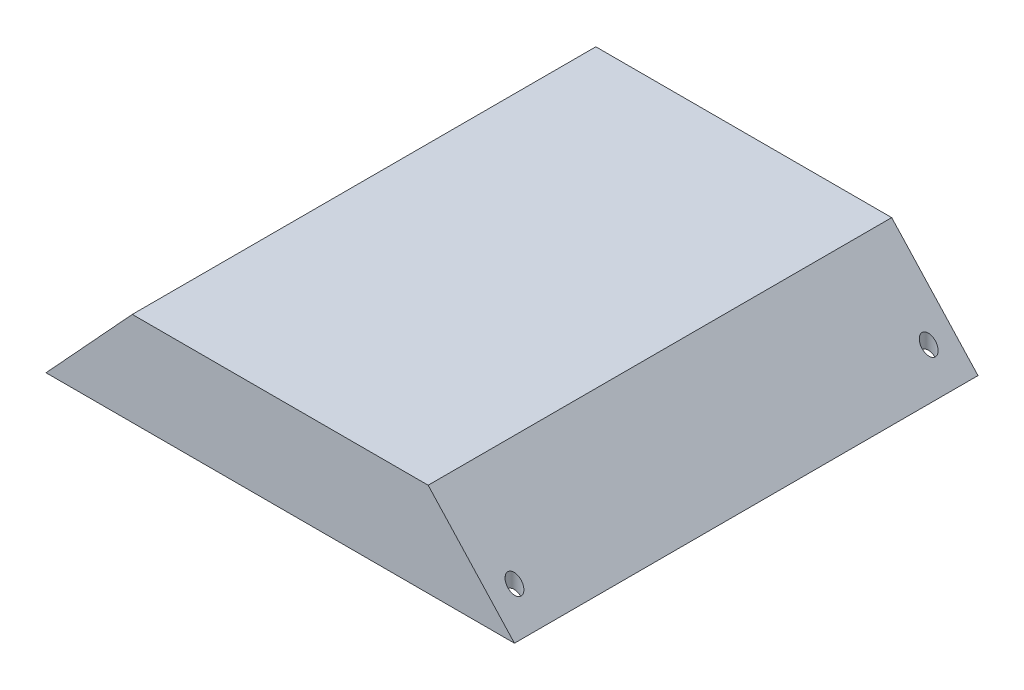
SolidWorks part; units mm, degrees
ref_plane "Alzado" through (0, 0, 0) normal (0, 0, 1) x (1, 0, 0)
ref_plane "Planta" through (0, 0, 0) normal (0, 1, 0) x (1, 0, 0)
ref_plane "Vista lateral" through (0, 0, 0) normal (1, 0, 0) x (0, 0, -1)
sketch "Croquis2" plane through (0, 0, 0) normal (0, 0, 1) x (1, 0, 0)
  line L0 (-47.5, 0) -> (-30, 0)
  line L1 (-30, 0) -> (-30, 19)
  line L2 (-30, 19) -> (-47.5, 0)
  line L3 (30, 19) -> (47.5, 0)
  line L4 (-30, 19) -> (30, 19)
  line L5 (-30, 19) -> (-30, 0)
  line L6 (-30, 0) -> (30, 0)
  line L7 (30, 19) -> (30, 0)
  line L8 (47.5, 0) -> (30, 0)
  dimension "D1" = 95
  dimension "D2" = 60
  dimension "D3" = 19
extrude "Saliente-Extruir1" add sketch "Croquis2" along normal blind 94 contours L7 L4 L1 L6 | L1 L2 L0 | L8 L3 L7 region at (-35.8333, 6.3333, 0) region at (0, 9.5, 0) region at (35.8333, 6.3333, 0)
sketch "Croquis3" plane through (0, 0, 0) normal (0, 0, -1) x (-1, 0, 0)
  line L0 (-44.7368, 0) -> (-30, 16)
  line L1 (47.5, 0) -> (-47.5, 0) construction
  line L2 (-30, 16) -> (30, 16)
  line L3 (30, 16) -> (44.7368, 0)
  line L4 (44.7368, 0) -> (-44.7368, 0)
  line L5 (-30, 19) -> (-47.5, 0) construction
  line L6 (30, 19) -> (-30, 19) construction
  line L7 (30, 19) -> (47.5, 0) construction
  line L11 (47.5, 0) -> (44.7368, 0)
  line M1 (-47.5, 0) -> (47.5, 0)
  dimension "D1" = 3
extrude "Cortar-Extruir1" cut sketch "Croquis3" against normal blind 91 contours L3 L2 L0 M1 region at (0, 7.4742, 0)
sketch "Croquis7" plane through (0, 19, 0) normal (0, 1, 0) x (1, 0, 0)
  line L0 (-47.5, -94) -> (-47.5, 0) construction
  line L1 (-47.5, 0) -> (47.5, 0) construction
  line L2 (47.5, 0) -> (47.5, -94) construction
  line L3 (47.5, -94) -> (-47.5, -94) construction
  line L4 (-42.5, 0) -> (-42.5, -94) construction
  line L5 (-47.5, -5) -> (47.5, -5) construction
  line L6 (42.5, 0) -> (42.5, -94) construction
  line L7 (-47.5, -89) -> (47.5, -89) construction
  dimension "D1" = 5
  dimension "D2" = 5
  dimension "D3" = 5
  dimension "D4" = 5
hole_wizard "Taladro de margen para M2.51" positions "Croquis11" profile "Croquis10" hole size "M2.5" standard "ISO" end condition through all
sketch "Croquis11" plane through (0, 19, 0) normal (0, 1, 0) x (1, 0, 0)
  line L0 (-42.5, 0) -> (-42.5, -94) construction
  line L1 (-47.5, -5) -> (47.5, -5) construction
  line L2 (42.5, 0) -> (42.5, -94) construction
  line L3 (-47.5, -89) -> (47.5, -89) construction
  point P0 (-42.5, -5)
  point P6 (42.5, -5)
  point P10 (-42.5, -89)
  point P14 (42.5, -89)
sketch "Croquis10" plane through (-42.5, 19, 5) normal (1, 0, 0) x (0, 0, 1)
  line L0 (0, 0) -> (0, 19)
  line L1 (0, 19) -> (1.35, 19)
  line L2 (1.35, 19) -> (1.35, 0)
  line L5 (1.35, 0) -> (0, 0)
  line L11 (0, -6.35) -> (0, 107.95) construction
  dimension "Diámetro de taladro hasta el siguiente" = 2.7
  dimension "Profundidad de taladro hasta el siguiente" = 19
